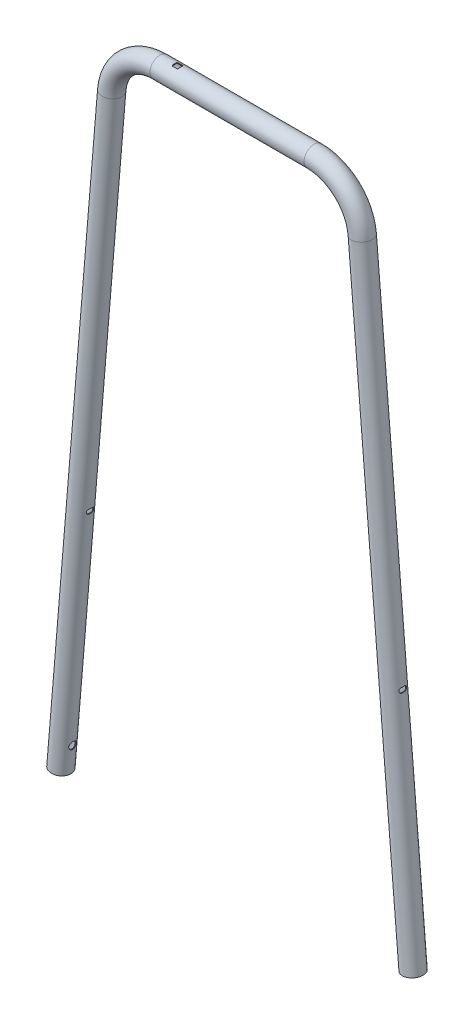
SolidWorks part; units mm, degrees
ref_plane "Front Plane" through (0, 0, 0) normal (0, 0, 1) x (1, 0, 0)
ref_plane "Top Plane" through (0, 0, 0) normal (0, 1, 0) x (1, 0, 0)
ref_plane "Right Plane" through (0, 0, 0) normal (1, 0, 0) x (0, 0, -1)
sketch "Sketch1" plane through (0, 0, 0) normal (0, 0, 1) x (1, 0, 0)
  line L0 (0, 0) -> (0, 595.2821) construction
  line L1 (0, 0) -> (414.971, 0) construction
  line L2 (-84.477, 556.716) -> (84.477, 556.716)
  line L3 (137.295, 508.1048) -> (193, -162.284)
  line L4 (-137.295, 508.1048) -> (-193, -162.284)
  line L5 (-193, -162.284) -> (-297.8448, -162.284) construction
  arc A0 (137.295, 508.1048) -> (84.477, 556.716) centre (84.477, 503.716) ccw
  arc A1 (-137.295, 508.1048) -> (-84.477, 556.716) centre (-84.477, 503.716) cw
  point P12 (133.2557, 556.716)
  point P17 (0, 556.716)
  dimension "D4" = 53
  dimension "D1" = 386
  dimension "D2" = 9.5
  dimension "D3" = 719
ref_plane "Plane1" through (-193, -162.284, 0) normal (-0.0828, -0.9966, 0) x (-0.9966, 0.0828, 0)
sketch "Sketch2" plane through (-193, -162.284, 0) normal (-0.0828, -0.9966, 0) x (-0.9966, 0.0828, 0)
  circle A0 centre (0, 0) radius 11
  circle A1 centre (0, 0) radius 10.2
  dimension "D1" = 0.8
sweep "Sweep2" add profiles "Sketch2" path "Sketch1"
sketch "Sketch6" plane through (-14.7157, -177.0983, 0) normal (-0.0828, -0.9966, 0) x (0.9966, -0.0828, 0)
  line L0 (-178.8987, 0) -> (-189.0987, 0)
  line L1 (-178.8987, 0) -> (-178.8987, 10.2)
  circle A0 centre (-178.8987, 0) radius 10.2 construction
  circle A1 centre (-178.8987, 0) radius 10.2 construction
ref_plane "Plane3" through (-193, -162.284, 0) normal (-0.9966, 0.0828, 0) x (0, 0, 1)
ref_plane "Plane4" through (0, 567.716, 0) normal (0, 1, 0) x (1, 0, 0)
sketch "Sketch17" plane through (-193, -162.284, 0) normal (-0.9966, 0.0828, 0) x (0, 0, 1)
  line L0 (0, 0) -> (0, 28.3) construction
  line L1 (-11, 0) -> (11, 0) construction
  line L2 (0, 28.3) -> (0, 133.9257) construction
  circle A0 centre (0, 28.3) radius 4
  dimension "D3" = 8
  dimension "D1" = 28.3
  dimension "D2" = 133.9257
extrude "Cut-Extrude6" cut sketch "Sketch17" against normal blind 50
sketch "Sketch18" plane through (-193, -162.284, 0) normal (-0.9966, 0.0828, 0) x (0, 0, 1)
  line L0 (0, 0) -> (0, 261.3035) construction
  line L1 (-10.2, 0) -> (10.2, 0) construction
  line L3 (-2, 263.8035) -> (2, 263.8035)
  line L4 (-4, 261.8035) -> (-4, 260.8035)
  line L5 (-2, 258.8035) -> (2, 258.8035)
  line L6 (4, 261.8035) -> (4, 260.8035)
  line L7 (-4, 263.8035) -> (4, 258.8035) construction
  line L8 (-4, 258.8035) -> (4, 263.8035) construction
  arc A0 (-2, 258.8035) -> (-4, 260.8035) centre (-2, 260.8035) cw
  arc A1 (4, 260.8035) -> (2, 258.8035) centre (2, 260.8035) cw
  arc A2 (2, 263.8035) -> (4, 261.8035) centre (2, 261.8035) cw
  arc A3 (-2, 263.8035) -> (-4, 261.8035) centre (-2, 261.8035) ccw
  dimension "D3" = 2
  dimension "D1" = 5
  dimension "D2" = 8
extrude "Cut-Extrude7" cut sketch "Sketch18" against normal blind 50 and the other way blind 50
mirror "Mirror2" about plane through (0, 0, 0) normal (1, 0, 0) of "Cut-Extrude6", "Cut-Extrude7"
sketch "Sketch19" plane through (-193, -162.284, 0) normal (-0.9966, 0.0828, 0) x (0, 0, 1)
  line L0 (0, 0) -> (0, 498) construction
  line L1 (-10.2, 0) -> (10.2, 0) construction
  circle A0 centre (0, 498) radius 4
  dimension "D1" = 498
extrude "Cut-Extrude8" cut sketch "Sketch19" along normal blind 50
sketch "Sketch20" plane through (0, 567.716, 0) normal (0, 1, 0) x (1, 0, 0)
  line L0 (-203.9622, 0) -> (-65.0622, 0) construction
  circle A0 centre (-65.0622, 0) radius 3.1
  ellipse E0 centre (-193, 0) end of major axis (-193, 11) minor radius 10.9622 construction
  dimension "D2" = 6.2
  dimension "D1" = 138.9
extrude "Cut-Extrude9" cut sketch "Sketch20" against normal blind 50
sketch "Sketch21" plane through (0, 567.716, 0) normal (0, 1, 0) x (1, 0, 0)
  line L0 (-203.9622, 0) -> (-65.0622, 0) construction
  line L2 (-67.3122, -3.1) -> (-62.8122, -3.1)
  line L3 (-68.3122, -2.1) -> (-68.3122, 2.1)
  line L4 (-67.3122, 3.1) -> (-62.8122, 3.1)
  line L5 (-61.8122, -2.1) -> (-61.8122, 2.1)
  line L6 (-68.3122, -3.1) -> (-61.8122, 3.1) construction
  line L7 (-68.3122, 3.1) -> (-61.8122, -3.1) construction
  arc A0 (-67.3122, 3.1) -> (-68.3122, 2.1) centre (-67.3122, 2.1) ccw
  arc A1 (-68.3122, -2.1) -> (-67.3122, -3.1) centre (-67.3122, -2.1) ccw
  arc A2 (-62.8122, 3.1) -> (-61.8122, 2.1) centre (-62.8122, 2.1) cw
  arc A3 (-61.8122, -2.1) -> (-62.8122, -3.1) centre (-62.8122, -2.1) cw
  ellipse E0 centre (-193, 0) end of major axis (-193, 11) minor radius 10.9622 construction
  dimension "D3" = 1
  dimension "D4" = 1
  dimension "D1" = 6.5
  dimension "D2" = 6.2
extrude "Cut-Extrude10" cut sketch "Sketch21" against normal blind 10
